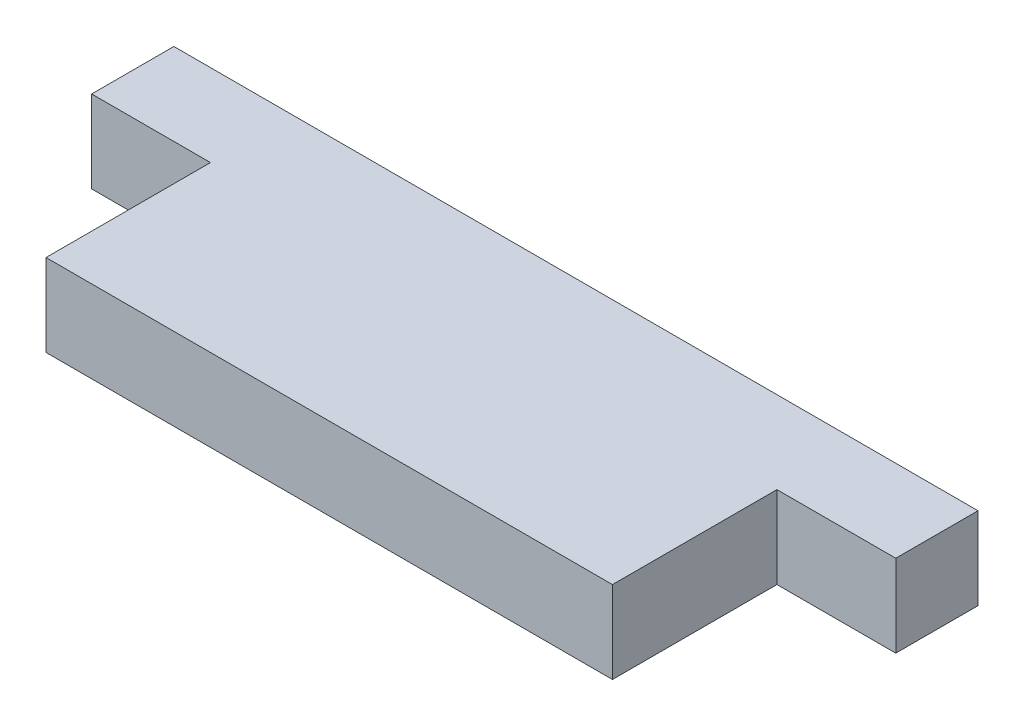
SolidWorks part; units mm, degrees
material "Beech"
ref_plane "Front Plane" through (0, 0, 0) normal (0, 0, 1) x (1, 0, 0)
ref_plane "Top Plane" through (0, 0, 0) normal (0, 1, 0) x (1, 0, 0)
ref_plane "Right Plane" through (0, 0, 0) normal (1, 0, 0) x (0, 0, -1)
sketch "Sketch1" plane through (0, 0, 0) normal (0, 1, 0) x (1, 0, 0)
  line L0 (0, 0) -> (0, 12.7)
  line L1 (0, 0) -> (43.74, 0)
  line L3 (43.74, 0) -> (43.74, 12.7)
  line L4 (-9.1751, 19.05) -> (52.9151, 19.05)
  line L5 (-9.1751, 19.05) -> (-9.1751, 12.7)
  line L6 (52.9151, 19.05) -> (52.9151, 12.7)
  line L7 (-9.1751, 12.7) -> (0, 12.7)
  line L8 (43.74, 12.7) -> (52.9151, 12.7)
  dimension "D1" = 12.7
  dimension "D2" = 43.74
  dimension "D3" = 6.35
  dimension "D4" = 9.1751
  dimension "D5" = 9.1751
extrude "Boss-Extrude1" add sketch "Sketch1" along normal blind 6.35
equation "\"MotorMountLegLength\"=.25in"
equation "\"GearOffset\"=.264907in"
equation "\"D4@Sketch1\"=\"TriggerRackOffset\"+.125in"
equation "\"D5@Sketch1\"=\"TriggerRackOffset\"+.125in"
equation "\"D2@Sketch1\" = \"CageLeftBottomEdge\" + \"CageRightBottomEdge\""
equation "\"CageLeftBottomEdge\"=22.11mm"
equation "\"CageLeftTopEdge\"=22.11mm"
equation "\"CageRightBottomEdge\"=21.63mm"
equation "\"CageRightTopEdge\"=21.63mm"
equation "\"CageHeight\"=86.04mm"
equation "\"CageLength\"=73.76mm"
equation "\"CageTopScrewClearance\"=10mm"
equation "\"CageBottomScrewClearance\"=25mm"
equation "\"CageLeftTopDepth\"= 11.65mm"
equation "\"CageLeftBottomDepth\"=11.11mm"
equation "\"CageLeftTopHeight\"=8.56175mm"
equation "\"CageLeftBottomHeight\"=16mm"
equation "\"CageRightTopDepth\"= 11.05mm"
equation "\"CageRightBottomDepth\"=10.58mm"
equation "\"CageRightTopHeight\"=9.6mm"
equation "\"CageRightBottomHeight\"=15.49mm"
equation "\"CageLeftTopChannelDepth\"=2.41908mm"
equation "\"CageLeftBottomChannelDepth\"=2.588mm"
equation "\"CageLeftChannelHeight\"=11.7mm"
equation "\"CageRightTopChannelDepth\"=2.32mm"
equation "\"CageRightBottomChannelDepth\"=2.318mm"
equation "\"CageRightChannelHeight\"=10mm"
equation "\"CageChanRelHeight\"=23.99mm"
equation "\"CageChanRelDepth\"=5.492mm"
equation "\"CageChamberRadius\"=16.261mm"
equation "\"CageScrewDiameter\"=4.8mm"
equation "\"CageSetScrewDiameter\"=3.5mm"
equation "\"CageAxleRadius\"=6.639mm"
equation "\"CageAxleKeyHeight\"=1.619mm"
equation "\"CageAxleKeyWidth\"=2.662mm"
equation "\"CageHoseWindowWidth\"=16.29mm"
equation "\"CageHoseWindowHeight\"=26.5mm"
equation "\"CageHoseWindow-Edge\"=8.89mm"
equation "\"CageScrew-VerticalEdge\"=5.0mm"
equation "\"CageScrew-HorizontalEdge\"=7.5mm"
equation "\"CageScrew-HoseCornerScrewEdge\"=4.45mm"
equation "\"CageAxle-BottomEdge\"=56.05mm"
equation "\"CageAxle-FrontEdge\"=46.03mm"
equation "\"CageBackSetScrew-Axle\"=40mm"
equation "\"CageFrontSetScrew-Axle\"=22mm"
equation "\"CageVelocityWindow-BackEdge\"=34.8mm"
equation "\"CageVelocityWindow-BottomEdge\"=27.55mm"
equation "\"CageVelocityWindowHeight\"=22.29mm"
equation "\"CageVelocityWindowWidth\"=12.61mm"
equation "\"TriggerSlot-BottomEdge\"=6.35mm"
equation "\"TriggerSlot-FrontEdge\"=15mm"
equation "\"TriggerSlotSize\"=6.7mm"
equation "\"TriggerRackOffset\"=.236224in"
equation "\"TriggerSlotSizeInt\"=.25in"
equation "\"TriggerSlotSpacing\"=.25in"
equation "\"TriggerMiniSlotWidth\"=3.5mm"
equation "\"TriggerRackWidth\"=6.5mm"
equation "\"TGMGearFaceDiameter\"=24.40mm"
equation "\"TGMCylinderLength\"=15.00mm"
equation "\"TGMScrewHole-Center\"=8.70mm"
equation "\"TGMScrewHoleDiameter\"=5.04mm"
equation "\"TGMCenterHoleDiameter\"=9.50mm"
equation "\"TGMShaftCollarSideLength\"=19.00mm"
equation "\"TGMShaftCollarDockingDepth\"=7.00mm"
equation "\"whitemotordepth\"=11.27mm"
equation "\"whitemotorbackdepth\"=3.845mm"
equation "\"whitemotoraxledepth\" = 3.5mm"
equation "\"whitemotoraxleoffset\"=11.4mm"
equation "\"whitemotorwidth\"=12.07mm"
equation "\"whitemotorheight\"=16.68mm"
equation "\"whitemotorcylinderlength\" =13.04mm"
equation "\"whitemotorcylinderradius\"=3.845mm"
equation "\"whitemotorcylinderoffset\"=2.35mm"
equation "\"whitemotorcutoutlength\"=1.88mm"
equation "\"whitemotorouterrad\"=5mm"
equation "\"whitemotorinnerrad\"=2.95mm"
equation "\"elasticracklength\"=2in"
equation "\"elasticrackpegsize\"=.25in"
equation "\"elasticrackpegbuffer\"=.125in"
equation "\"elasticrackpegspacing\"=1.76476378in"
equation "\"elasticbaybuffer\"=.25in"
equation "\"elasticdepth\"=.125in"
equation "\"elasticbaydepth\"=.75in"
equation "\"motormountwidth\"=12mm"
equation "\"motormountcornerfillet\"=3mm"
equation "\"pandiscradius\"=14in"
equation "\"towermaterialwidth\"=.25in"
equation "\"towerslotlength\"=.5in"
equation "\"towermarkerspace\"=5in"
equation "\"towerslothorizoffset\"=1in"
equation "\"towerslothorizspacing\"=2in"
equation "\"towerslotvertoffset\"=3in"
equation "\"towerslotvertspacing\"=2in"
equation "\"towerheight\"=12in"
equation "\"towerupslot\"=1in"
equation "\"toweraxle\"=.5in"
equation "\"towerplatslotoffset\"=1.5in"
equation "\"towermotorpanelheight\"=10in"
equation "\"towerplatdepth\"=2in"
equation "\"stepperouterrad\"=10mm"
equation "\"stepperscrewsize\"=3.45mm"
equation "\"stepperscrewc2c\"=49.5mm"
equation "\"stepperdepthoffset\"=24mm"
equation "\"stepperhorizoffset\"=22.91mm"
equation "\"shaftslotOD\"=18.8mm"
equation "\"shaftslotID\"=13.28mm"
equation "\"shaftkeywidth\"=2.67mm"
equation "\"shaftkeydepth\"=1.8mm"
equation "\"shaftcollartotaldepth\"=12.5mm"
equation "\"shaftsquaredepth\"=6mm"
equation "\"shaftsetscrewsize\"=3.5mm"
equation "\"shaftkeytightdepth\"=1.85mm"
equation "\"shaftslottightID\"=12.78mm"
equation "\"shaftsetscrewoffset\"=9mm"
equation "\"cagecollartotaldepth\"=10mm"
equation "\"cagecollartotalwidth\"=35mm"
equation "\"cagecollarbasedepth\"=4mm"
